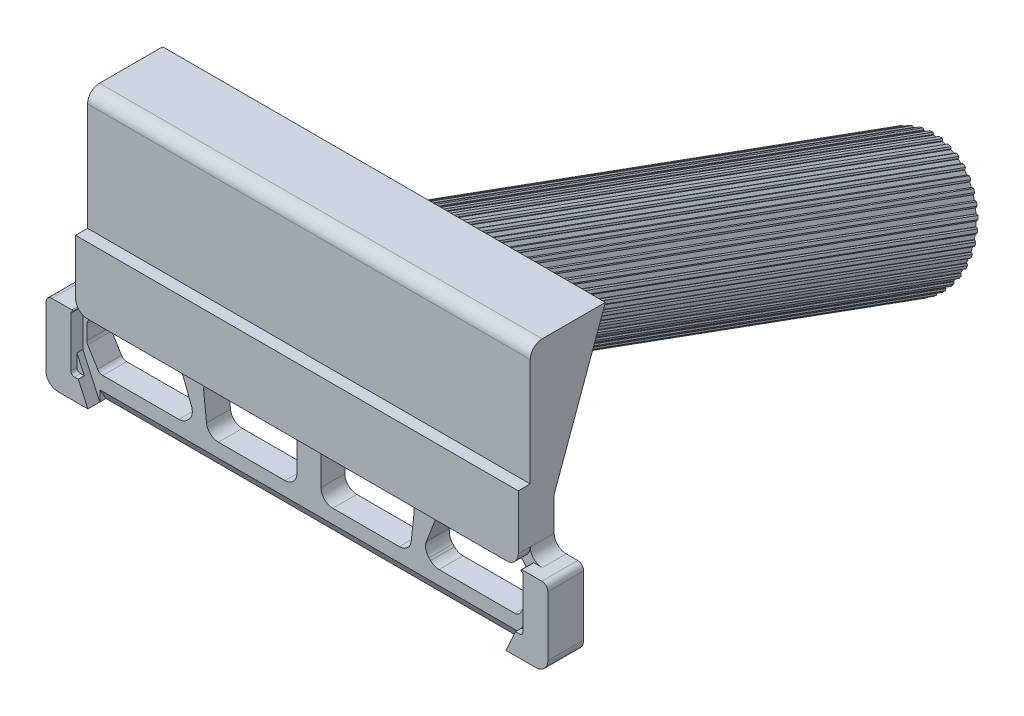
SolidWorks part; units mm, degrees
ref_plane "Front Plane" through (0, 0, 0) normal (0, 0, 1) x (1, 0, 0)
ref_plane "Top Plane" through (0, 0, 0) normal (0, 1, 0) x (1, 0, 0)
ref_plane "Right Plane" through (0, 0, 0) normal (1, 0, 0) x (0, 0, -1)
sketch "base plate" plane through (0, 0, 0) normal (0, 0, 1) x (1, 0, 0)
  line L0 (19.4937, 6.5) -> (20.4641, 6.5)
  line L1 (-18.4937, 12.0545) -> (-18.4937, 7.5)
  line L2 (20.9641, 6) -> (20.9641, 1)
  line L3 (19.9641, 0) -> (-19.9641, 0)
  line L4 (2.0062, 6.5) -> (7.9562, 6.5)
  line L5 (18.0111, 6.0574) -> (18.4651, 5.381)
  line L7 (18.4761, 3.6343) -> (17.6502, 2.2885)
  line L9 (18.4937, 7.5) -> (18.4937, 12.0545)
  line L10 (18.4937, 12.0545) -> (-18.4937, 12.0545)
  line L12 (18.55, 5.1023) -> (18.55, 3.8958)
  line L13 (7.558, 2.05) -> (2.0062, 2.05)
  line L14 (11.6407, 6.5) -> (17.1808, 6.5)
  line L16 (1.0062, 5.5) -> (1.0062, 3.05)
  line L21 (7.9562, 6.5) -> (8.5017, 5.9545)
  line L22 (8.7888, 5.1403) -> (8.5523, 2.943)
  line L23 (10.8704, 2.05) -> (17.2241, 2.05)
  line L24 (10.1633, 2.3429) -> (10.0333, 2.4728)
  line L25 (9.8082, 3.5417) -> (10.7085, 5.8618)
  line L31 (-9.8082, 3.5417) -> (-10.7085, 5.8618)
  line L33 (18.4937, 12.0545) -> (18.4937, 7.5)
  line L36 (-10.1633, 2.3429) -> (-10.0333, 2.4728)
  line L43 (0, 12.0545) -> (0, 0) construction
  line L44 (-10.8704, 2.05) -> (-17.2241, 2.05)
  line L45 (-8.7888, 5.1403) -> (-8.5523, 2.943)
  line L46 (-7.9562, 6.5) -> (-8.5017, 5.9545)
  line L47 (-1.0062, 5.5) -> (-1.0062, 3.05)
  line L48 (-11.6407, 6.5) -> (-17.1808, 6.5)
  line L49 (-7.558, 2.05) -> (-2.0062, 2.05)
  line L50 (-18.55, 5.1023) -> (-18.55, 3.8958)
  line L51 (-18.4937, 7.5) -> (-18.4937, 12.0545)
  line L52 (-18.4761, 3.6343) -> (-17.6502, 2.2885)
  line L53 (-18.0111, 6.0574) -> (-18.4651, 5.381)
  line L54 (-2.0062, 6.5) -> (-7.9562, 6.5)
  line L55 (-20.9641, 6) -> (-20.9641, 1)
  line L56 (-19.4937, 6.5) -> (-20.4641, 6.5)
  arc A0 (18.4937, 7.5) -> (19.4937, 6.5) centre (19.4937, 7.5) ccw
  arc A2 (17.2241, 2.05) -> (17.6502, 2.2885) centre (17.2241, 2.55) ccw
  arc A3 (18.4761, 3.6343) -> (18.55, 3.8958) centre (18.05, 3.8958) ccw
  arc A4 (18.4651, 5.381) -> (18.55, 5.1023) centre (18.05, 5.1023) cw
  arc A5 (20.9641, 6) -> (20.4641, 6.5) centre (20.4641, 6) ccw
  arc A6 (19.9641, 0) -> (20.9641, 1) centre (19.9641, 1) ccw
  arc A7 (7.558, 2.05) -> (8.5523, 2.943) centre (7.558, 3.05) ccw
  arc A8 (8.7888, 5.1403) -> (8.5017, 5.9545) centre (7.7946, 5.2474) ccw
  arc A9 (10.0333, 2.4728) -> (9.8082, 3.5417) centre (10.7404, 3.1799) cw
  arc A10 (10.1633, 2.3429) -> (10.8704, 2.05) centre (10.8704, 3.05) ccw
  arc A11 (11.6407, 6.5) -> (10.7085, 5.8618) centre (11.6407, 5.5) ccw
  arc A12 (2.0062, 2.05) -> (1.0062, 3.05) centre (2.0062, 3.05) cw
  arc A13 (2.0062, 6.5) -> (1.0062, 5.5) centre (2.0062, 5.5) ccw
  arc A29 (18.0111, 6.0574) -> (17.1808, 6.5) centre (17.1808, 5.5) ccw
  arc A30 (-18.0111, 6.0574) -> (-17.1808, 6.5) centre (-17.1808, 5.5) cw
  arc A31 (-2.0062, 6.5) -> (-1.0062, 5.5) centre (-2.0062, 5.5) cw
  arc A32 (-2.0062, 2.05) -> (-1.0062, 3.05) centre (-2.0062, 3.05) ccw
  arc A33 (-11.6407, 6.5) -> (-10.7085, 5.8618) centre (-11.6407, 5.5) cw
  arc A34 (-10.1633, 2.3429) -> (-10.8704, 2.05) centre (-10.8704, 3.05) cw
  arc A35 (-10.0333, 2.4728) -> (-9.8082, 3.5417) centre (-10.7404, 3.1799) ccw
  arc A36 (-8.7888, 5.1403) -> (-8.5017, 5.9545) centre (-7.7946, 5.2474) cw
  arc A37 (-7.558, 2.05) -> (-8.5523, 2.943) centre (-7.558, 3.05) cw
  arc A38 (-19.9641, 0) -> (-20.9641, 1) centre (-19.9641, 1) cw
  arc A39 (-20.9641, 6) -> (-20.4641, 6.5) centre (-20.4641, 6) cw
  arc A40 (-18.4651, 5.381) -> (-18.55, 5.1023) centre (-18.05, 5.1023) ccw
  arc A41 (-18.4761, 3.6343) -> (-18.55, 3.8958) centre (-18.05, 3.8958) cw
  arc A42 (-17.2241, 2.05) -> (-17.6502, 2.2885) centre (-17.2241, 2.55) cw
  arc A43 (-18.4937, 7.5) -> (-19.4937, 6.5) centre (-19.4937, 7.5) cw
  point P2 (0, 0)
  point P3 (0, 0)
  point P4 (0, 0)
  point P12 (0, 0)
  point P13 (0, 0)
  point P15 (0, 0)
  point P16 (3.7228, 0)
  point P19 (0, 0)
  point P20 (0, 0)
  point P21 (0, 0)
  point P23 (0, 0)
  point P24 (0, 0)
  point P28 (0, 0)
  point P103 (0, 0)
  point P104 (17.2241, 2.4728)
  point P105 (17.2241, 2.4728)
  point P106 (-2.0062, 5.5)
  point P107 (2.0062, 6.5)
  point P108 (0, 0)
  point P109 (-2.0062, 5.5)
  point P110 (-2.0062, 6.5)
  point P111 (0, 0)
  point P112 (18.4651, 5.1023)
  dimension "D3" = 4.45
  dimension "D7" = 0.5
  dimension "D6" = 20.9641
  dimension "D1" = 12.0545
  dimension "D2" = 2.05
  dimension "D4" = 6.5
  dimension "D8" = 0.4704
  dimension "D5" = 1
  dimension "D9" = 1
  dimension "D10" = 6.95
  dimension "D11" = 2.45
  dimension "D12" = 0.7715
  dimension "D16" = 10.8704
  dimension "D23" = 0.5
  dimension "D20" = 5.1023
  dimension "D13" = 7.9562
  dimension "D14" = 8.5017
  dimension "D15" = 8.5523
  dimension "D17" = 9.8082
  dimension "D18" = 3.5417
  dimension "D19" = 0.1838
  dimension "D21" = 3.6343
  dimension "D22" = 1.579
  dimension "D24" = 0.8146
  dimension "D25" = 18.0111
  dimension "D27" = 6.0574
extrude "Boss-Extrude3" add sketch "base plate" along normal blind 2 contours L3 A6 L2 A5 L0 A0 L9 L10 A29 L5 A4 L12 A3 L7 A2 L23 A10 L24 A9 L25 A11 L14 A13 L4 L21 A8 L22 A7 L13 A12 L16 | L43 L10 L1 A43 L56 A39 L55 A38 L3 L44 A42 L52 A41 L50 A40 L53 A30 L48 A33 L31 A35 L36 A34 L49 A37 L45 A36 L46 L54 A31 L47 A32 region at (10.051, 6.4857, 0) region at (-10.051, 6.4857, 0)
sketch "Sketch3" plane through (0, 0, 2) normal (0, 0, 1) x (1, 0, 0)
  line L16 (0, 0) -> (0, 12.0545) construction
  line L17 (18.4937, 12.0545) -> (-18.4937, 12.0545) construction
  line L18 (-18.4937, 12.0545) -> (18.4937, 12.0545)
  line L19 (18.4937, 12.0545) -> (18.4937, 7.5)
  line L20 (-17.4937, 6.5) -> (17.4937, 6.5)
  line L21 (2.0062, 6.5) -> (7.9562, 6.5) construction
  line L22 (-18.4937, 12.0545) -> (-18.4937, 7.5)
  arc A6 (17.4937, 6.5) -> (18.4937, 7.5) centre (17.4937, 7.5) ccw
  arc A7 (-17.4937, 6.5) -> (-18.4937, 7.5) centre (-17.4937, 7.5) cw
  point P10 (0, 7.6292)
  point P16 (0, 6.5)
  dimension "D1" = 1
extrude "Boss-Extrude4" add sketch "Sketch3" along normal blind 1
sketch "pill" plane through (0, 0, 3) normal (0, 0, 1) x (1, 0, 0)
  line L14 (20.9641, 6) -> (18.8845, 6)
  line L19 (18.7281, 6.43) -> (18.7281, 6.4096)
  line L21 (18.7981, 6.3396) -> (18.8145, 6.3396)
  line L22 (19.4937, 6.5) -> (20.4641, 6.5) construction
  line L23 (18.7981, 6.5) -> (20.4641, 6.5)
  line L24 (18.8845, 6) -> (18.8845, 6.2696)
  line L26 (0, -1.1) -> (0, 1.1) construction
  line L27 (-18.8845, 6) -> (-18.8845, 6.2696)
  line L28 (-18.7981, 6.5) -> (-20.4641, 6.5)
  line L29 (-18.7981, 6.3396) -> (-18.8145, 6.3396)
  line L30 (-18.7281, 6.43) -> (-18.7281, 6.4096)
  line L31 (-20.9641, 6) -> (-18.8845, 6)
  arc A11 (18.7981, 6.5) -> (18.7281, 6.43) centre (18.7981, 6.43) ccw
  arc A12 (18.8145, 6.3396) -> (18.8845, 6.2696) centre (18.8145, 6.2696) cw
  arc A13 (18.7281, 6.4096) -> (18.7981, 6.3396) centre (18.7981, 6.4096) ccw
  arc A14 (20.9641, 6) -> (20.4641, 6.5) centre (20.4641, 6) ccw construction
  arc A15 (20.9641, 6) -> (20.4641, 6.5) centre (20.4641, 6) ccw
  arc A16 (-20.9641, 6) -> (-20.4641, 6.5) centre (-20.4641, 6) cw
  arc A17 (-18.7281, 6.4096) -> (-18.7981, 6.3396) centre (-18.7981, 6.4096) cw
  arc A18 (-18.8145, 6.3396) -> (-18.8845, 6.2696) centre (-18.8145, 6.2696) ccw
  arc A19 (-18.7981, 6.5) -> (-18.7281, 6.43) centre (-18.7981, 6.43) cw
  point P14 (0, 0)
  point P16 (0, 0)
  point P17 (0, 0)
  point P18 (0, 0)
  point P19 (0, 0)
  point P20 (0, 0)
  dimension "D4" = 0.0164
  dimension "D3" = 0.2696
  dimension "D1" = 0.07
  dimension "D2" = 18.7281
  dimension "D5" = 0.0204
extrude "pill extrude" add sketch "pill" against normal up to surface (1 mm away) contours L21 | A19 L28 A16 L31 L27 A18 L29 A17 L30 region at (19.8486, 6.2466, 3) region at (-19.8486, 6.2466, 3) up to face at (0, 4.3594, 2)
sketch "pods" plane through (0, 0, 2) normal (0, 0, 1) x (1, 0, 0)
  line L2 (20.9641, 6) -> (18.8845, 6) construction
  line L6 (19.9641, 0) -> (-19.9641, 0) construction
  line L7 (20.9641, 6) -> (20.9641, 1) construction
  line L14 (20.9641, 6) -> (18.8845, 6)
  line L15 (19.9641, 0) -> (17.4641, 0)
  line L20 (20.9641, 6) -> (20.9641, 1)
  line L21 (18.8845, 6) -> (18.8845, 3.1)
  line L22 (18.8845, 3.1) -> (17.4641, 0)
  line L23 (0, 0) -> (0, 12.0545) construction
  line L24 (18.4937, 12.0545) -> (-18.4937, 12.0545) construction
  line L25 (-18.8845, 3.1) -> (-17.4641, 0)
  line L26 (-18.8845, 6) -> (-18.8845, 3.1)
  line L27 (-20.9641, 6) -> (-20.9641, 1)
  line L28 (-19.9641, 0) -> (-17.4641, 0)
  line L29 (-20.9641, 6) -> (-18.8845, 6)
  arc A0 (19.9641, 0) -> (20.9641, 1) centre (19.9641, 1) ccw construction
  arc A2 (19.9641, 0) -> (20.9641, 1) centre (19.9641, 1) ccw
  arc A3 (-19.9641, 0) -> (-20.9641, 1) centre (-19.9641, 1) cw
  point P14 (0, 0)
  dimension "D1" = 3.5
  dimension "D2" = 3.1
extrude "Boss-Extrude7" add sketch "pods" along normal blind 1 contours L15 A2 L20 L14 L21 L22 | A3 L28 L25 L26 L29 L27
sketch "Sketch6" plane through (0, 0, 0) normal (0, 0, 1) x (1, 0, 0)
  line L0 (-18.5845, 0) -> (18.5845, 0)
  line L1 (18.8845, 0.3) -> (18.8845, 6.2696)
  line L2 (18.7981, 6.5) -> (21.4, 6.5)
  line L3 (21.6, 6.7) -> (21.6, 10.8413)
  line L4 (21.6, 10.8413) -> (-21.6, 10.8413)
  line L5 (0, 10.8413) -> (0, 0) construction
  line L10 (18.7281, 6.43) -> (18.7281, 6.4096)
  line L11 (18.7981, 6.3396) -> (18.8145, 6.3396)
  line L12 (-18.7981, 6.3396) -> (-18.8145, 6.3396)
  line L13 (-18.7281, 6.43) -> (-18.7281, 6.4096)
  line L15 (-21.6, 6.7) -> (-21.6, 10.8413)
  line L16 (-18.7981, 6.5) -> (-21.4, 6.5)
  line L17 (-18.8845, 0.3) -> (-18.8845, 6.2696)
  line L18 (17.4641, 0) -> (-17.4641, 0) construction
  line L20 (-18.8845, 3.1) -> (-18.8845, 6.2696) construction
  line L21 (-18.7981, 6.5) -> (-20.4641, 6.5) construction
  line L22 (18.8845, 3.1) -> (18.8845, 6.2696) construction
  line L23 (-18.7281, 6.4096) -> (-18.7281, 6.43) construction
  arc A1 (18.5845, 0) -> (18.8845, 0.3) centre (18.5845, 0.3) ccw
  arc A2 (18.7981, 6.5) -> (18.7281, 6.43) centre (18.7981, 6.43) ccw
  arc A3 (18.8145, 6.3396) -> (18.8845, 6.2696) centre (18.8145, 6.2696) cw
  arc A4 (18.7281, 6.4096) -> (18.7981, 6.3396) centre (18.7981, 6.4096) ccw
  arc A5 (21.4, 6.5) -> (21.6, 6.7) centre (21.4, 6.7) ccw
  arc A6 (-21.4, 6.5) -> (-21.6, 6.7) centre (-21.4, 6.7) cw
  arc A7 (-18.7281, 6.4096) -> (-18.7981, 6.3396) centre (-18.7981, 6.4096) cw
  arc A8 (-18.8145, 6.3396) -> (-18.8845, 6.2696) centre (-18.8145, 6.2696) ccw
  arc A9 (-18.7981, 6.5) -> (-18.7281, 6.43) centre (-18.7981, 6.43) cw
  arc A10 (-18.5845, 0) -> (-18.8845, 0.3) centre (-18.5845, 0.3) cw
  dimension "D5" = 0.07
  dimension "D6" = 0.3
  dimension "D7" = 0.2
  dimension "D1" = 4.3413
  dimension "D3" = 21.6
sketch "Sketch7" plane through (0, 0, 3) normal (0, 0, 1) x (1, 0, 0)
  line L5 (-18.5845, 1.75) -> (18.5845, 1.75)
  line L16 (18.8845, 2.05) -> (18.8845, 6.2696)
  line L18 (0, 0) -> (0, 8.3662) construction
  line L19 (18.8845, 6.2696) -> (-18.8845, 6.2696)
  line L20 (18.8845, 3.1) -> (18.8845, 6.2696) construction
  line L21 (-18.8845, 2.05) -> (-18.8845, 6.2696)
  arc A10 (18.5845, 1.75) -> (18.8845, 2.05) centre (18.5845, 2.05) ccw
  arc A11 (-18.5845, 1.75) -> (-18.8845, 2.05) centre (-18.5845, 2.05) cw
  point P12 (0, 6.2696)
  point P13 (0, 1.75)
  dimension "D2" = 6.2696
  dimension "D3" = 0.3
  dimension "D1" = 4.5196
extrude "Cut-Extrude2" cut sketch "Sketch7" against normal blind 0.5
sketch "Sketch12" plane through (0, 0, 0) normal (1, 0, 0) x (0, 0, -1)
  line L0 (-2, 12.0545) -> (-2, 21.0545)
  line L4 (0, 10.3066) -> (4.2759, 22.0545)
  line L5 (-1, 22.0545) -> (4.2759, 22.0545)
  line L6 (-2, 12.0545) -> (0, 10.3066)
  line L7 (-3, 12.0545) -> (0, 12.0545) construction
  line L8 (0, 7.5) -> (0, 12.0545) construction
  arc A0 (-2, 21.0545) -> (-1, 22.0545) centre (-1, 21.0545) cw
  point P8 (-2, 22.0545)
  point P13 (0, 0)
  point P14 (0, 0)
  dimension "D2" = 1
  dimension "D1" = 10
  dimension "D3" = 11.7479
  dimension "D4" = 20
  dimension "D5" = 48.848
extrude "Boss-Extrude11" add sketch "Sketch12" along normal up to surface and the other way up to surface up to face at (18.4937, 9.3218, 1.6) other way up to face at (-18.4937, 9.3218, 1.6)
ref_plane "Plane1" through (0, 1.2056, 3.3125) normal (0, -0.342, -0.9397) x (-1, 0, 0)
sketch "Sketch28" plane through (0, 1.2056, 3.3125) normal (0, -0.342, -0.9397) x (-1, 0, 0)
  circle A0 centre (0, 14) radius 5
  circle A1 centre (0, 14) radius 2.5
  point P3 (0, 0)
  dimension "D1" = 10
  dimension "D2" = 5
  dimension "D3" = 14
extrude "Boss-Extrude12" add sketch "Sketch28" along normal blind 50 contours A0 A1 region at (4.8586, 14.3613, -1.4758)
sketch "Sketch30" plane through (0, -15.8954, -43.6722) normal (0, -0.342, -0.9397) x (-1, 0, 0)
  line L0 (0, 14) -> (5.1304, 13.5511)
  line L1 (0, 14) -> (5.15, 14)
  circle A0 centre (0, 14) radius 4.95
  circle A1 centre (0, 14) radius 5.15
  circle M4 centre (0, 14) radius 5
  dimension "D1" = 10.3
  dimension "D2" = 9.9
  dimension "D3" = 5
extrude "Boss-Extrude13" add sketch "Sketch30" against normal blind 45 contours L0 A1 L1 M4 region at (-5.0689, -2.9476, -48.3847)
chamfer "Chamfer3" distance 0.1 angle 45 2 edges at (-5.1304, 4.534, -27.1638) (-5.15, 4.9558, -27.3174) tangent propagation no
pattern_circular "CirPattern1" count 40 over 360 about axis through (0, -2.7397, -48.4604) along (0, -0.342, -0.9397) of "Boss-Extrude13", "Chamfer3"
sketch "Sketch31" plane through (0, 0, 0) normal (1, 0, 0) x (0, 0, -1)
  line L6 (-2.5, 1.75) -> (-0.8595, -1.0914)
  line L7 (-2.5, 1.75) -> (-4.2635, 1.75)
  line L8 (-4.2635, 1.75) -> (-4.2635, -1.0914)
  line L9 (-4.2635, -1.0914) -> (-0.8595, -1.0914)
  line L10 (-3, 0) -> (0, 0) construction
  dimension "D1" = 120
  dimension "D2" = 3.404
  dimension "D3" = 2.8414
extrude "Cut-Extrude11" cut sketch "Sketch31" along normal up to vertex (17.4641 mm away) and the other way up to vertex (17.4641 mm away) up to point (17.4641, 0, 3) other way up to point (-17.4641, 0, 3)
